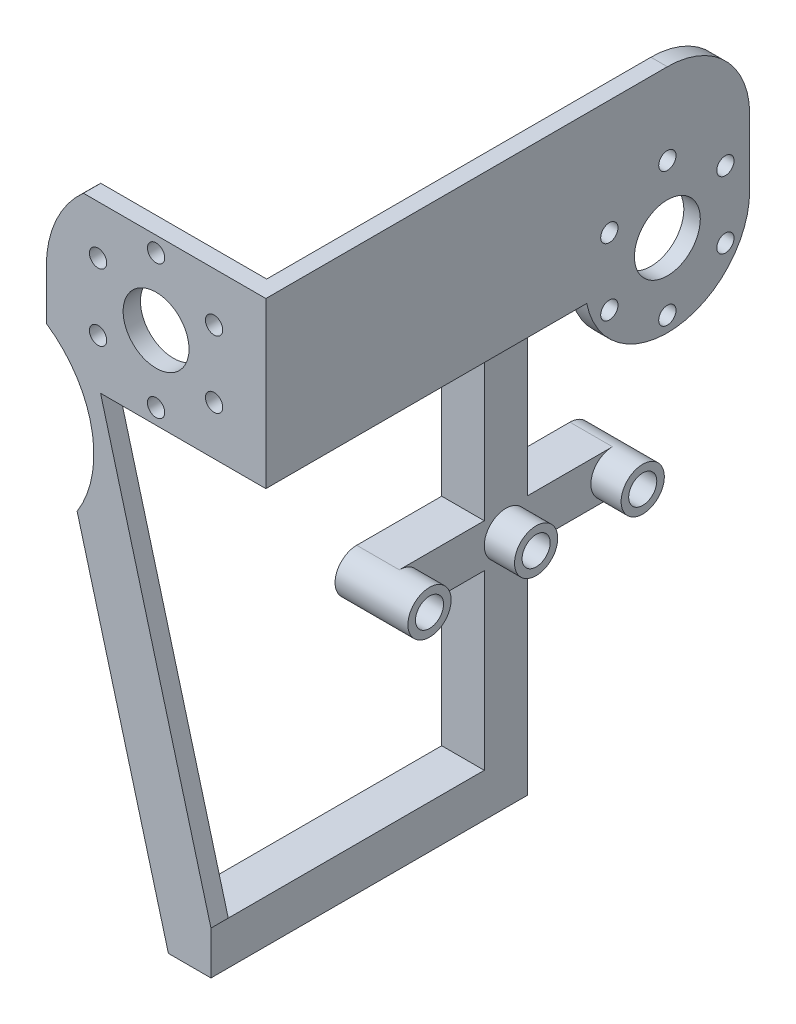
SolidWorks part; units mm, degrees
ref_plane "Front Plane" through (0, 0, 0) normal (0, 0, 1) x (1, 0, 0)
ref_plane "Top Plane" through (0, 0, 0) normal (0, 1, 0) x (1, 0, 0)
ref_plane "Right Plane" through (0, 0, 0) normal (1, 0, 0) x (0, 0, -1)
sketch "Sketch1" plane through (0, 0, 0) normal (0, 0, 1) x (1, 0, 0)
  line L1 (-25.4, -19.05) -> (25.4, -19.05)
  line L2 (-25.4, -19.05) -> (-25.4, 19.05)
  line L3 (-25.4, 19.05) -> (25.4, 19.05)
  line L4 (25.4, -19.05) -> (25.4, 19.05)
  line L5 (-25.4, -19.05) -> (25.4, 19.05) construction
  line L6 (-25.4, 19.05) -> (25.4, -19.05) construction
  circle A0 centre (0, 0) radius 15.5 construction
  circle A1 centre (0, 15.5) radius 2
  circle A2 centre (13.4234, 7.75) radius 2
  circle A3 centre (13.4234, -7.75) radius 2
  circle A4 centre (0, -15.5) radius 2
  circle A5 centre (-13.4234, -7.75) radius 2
  circle A6 centre (-13.4234, 7.75) radius 2
  circle A7 centre (0, 0) radius 7.62
  point P0 (0, 0)
  point P22 (0, 0)
  dimension "D2" = 31
  dimension "D3" = 4
  dimension "D5" = 15.24
  dimension "D1" = 38.1
  dimension "D6" = 50.8
  dimension "D4" = 6
extrude "Boss-Extrude1" add sketch "Sketch1" along normal blind 4
sketch "Sketch2" plane through (0, 0, 4) normal (0, 0, 1) x (1, 0, 0)
  line L2 (-16.8005, 19.05) -> (-25.4, 19.05)
  line L3 (-25.4, 19.05) -> (-25.4, 0)
  line L7 (25.4, 19.05) -> (-25.4, 19.05) construction
  arc A0 (-16.8005, 19.05) -> (-25.4, 0) centre (0, 0) ccw
  point P2 (-19.05, 0)
  point P3 (0, 19.05)
  point P4 (-4.1205, 19.05)
  point P5 (0, 0)
  point P6 (-16.8005, 19.05)
extrude "Cut-Extrude1" cut sketch "Sketch2" against normal up to next
sketch "Sketch4" plane through (25.4, 0, 0) normal (1, 0, 0) x (0, 0, -1)
  line L0 (-4, -19.05) -> (0, -19.05) construction
  line L1 (-4, 19.05) -> (88.9, 19.05)
  line L2 (-4, 19.05) -> (-4, -19.05)
  line L3 (-4, -19.05) -> (88.9, -19.05)
  line L4 (88.9, 19.05) -> (88.9, -19.05)
  line L5 (0, -19.05) -> (0, 19.05) construction
  line L7 (107.95, 0) -> (69.85, 0)
  line L8 (107.95, 0) -> (107.95, -15.24)
  line L9 (107.95, -15.24) -> (69.85, -15.24)
  line L10 (69.85, 0) -> (69.85, -15.24)
  circle A0 centre (88.9, 0) radius 19.05
  circle A1 centre (88.9, -15.24) radius 19.05
  dimension "D1" = 88.9
  dimension "D2" = 15.24
extrude "Boss-Extrude2" add sketch "Sketch4" against normal blind 3.81 contours L2 L1 L4 L3 | A0 | L8 L7 L10 L9 | A1
sketch "Sketch5" plane through (25.4, 0, 0) normal (1, 0, 0) x (0, 0, -1)
  circle A0 centre (88.9, -15.24) radius 7.62
  circle A2 centre (88.9, -15.24) radius 15.5 construction
  circle A3 centre (88.9, 0.26) radius 2
  circle A4 centre (102.3234, -7.49) radius 2
  circle A5 centre (102.3234, -22.99) radius 2
  circle A6 centre (88.9, -30.74) radius 2
  circle A7 centre (75.4766, -22.99) radius 2
  circle A8 centre (75.4766, -7.49) radius 2
  arc A9 (70.2349, -19.05) -> (107.95, -15.24) centre (88.9, -15.24) ccw construction
  dimension "D1" = 15.24
  dimension "D2" = 31
  dimension "D3" = 4
  dimension "D4" = 6
extrude "Cut-Extrude2" cut sketch "Sketch5" against normal up to next
sketch "Sketch6" plane through (0, -19.05, 0) normal (0, -1, 0) x (1, 0, 0)
  line L0 (25.4, 4) -> (25.4, -70.2349) construction
  line L1 (25.4, -59.2349) -> (6.35, -59.2349)
  line L2 (25.4, -59.2349) -> (25.4, -69.2349)
  line L3 (25.4, -69.2349) -> (6.35, -69.2349)
  line L4 (6.35, -59.2349) -> (6.35, -69.2349)
  line L5 (25.4, -70.2349) -> (21.59, -70.2349) construction
  dimension "D1" = 10
  dimension "D2" = 19.05
  dimension "D3" = 1
extrude "Boss-Extrude3" add sketch "Sketch6" against normal blind 10
sketch "Sketch9" plane through (6.35, 0, 0) normal (-1, 0, 0) x (0, 0, 1)
  line L0 (-59.2349, -9.05) -> (-59.2349, -19.05) construction
  line L1 (-69.2349, -9.05) -> (-59.2349, -9.05)
  line L2 (-69.2349, -9.05) -> (-69.2349, -63.45)
  line L3 (-88.9, -73.45) -> (-39.5698, -73.45)
  line L4 (-59.2349, -9.05) -> (-59.2349, -63.45)
  line L5 (-64.2349, -9.05) -> (-64.2349, -73.45) construction
  line L6 (-88.9, -7.62) -> (-88.9, -22.86) construction
  line L7 (-59.2349, -63.45) -> (-39.5698, -63.45)
  line L8 (-64.2349, -63.45) -> (-64.2349, -73.45)
  line L9 (-64.2349, -73.45) -> (-39.5698, -73.45)
  line L11 (-69.2349, -63.45) -> (-88.9, -63.45)
  line L12 (-64.2349, -63.45) -> (-64.2349, -73.45)
  line L13 (-64.2349, -73.45) -> (-88.9, -73.45)
  circle A0 centre (-88.9, -15.24) radius 7.62 construction
  circle A1 centre (-64.2349, -68.45) radius 5 construction
  circle A2 centre (-64.2349, -68.45) radius 3.25
  arc A3 (-88.9, -63.45) -> (-88.9, -73.45) centre (-88.9, -68.45) ccw
  circle A4 centre (-88.9, -68.45) radius 3.25
  circle A5 centre (-39.5698, -68.45) radius 3.25
  arc A6 (-39.5698, -63.45) -> (-39.5698, -73.45) centre (-39.5698, -68.45) cw
  point P2 (-39.3806, -73.45)
  line M5 (-69.2349, -19.05) -> (-59.2349, -19.05)
  dimension "D2" = 10
  dimension "D3" = 6.5
  dimension "D1" = 58.21
extrude "Boss-Extrude6" add sketch "Sketch9" against normal blind 6.35 and the other way blind 3.5 contours A6 L7 L4 L2 L11 A3 L3 A2 A4 A5 M5 region at (6.35, -55.2699, -64.2349)
sketch "Sketch10" plane through (12.7, 0, 0) normal (1, 0, 0) x (0, 0, -1)
  line L1 (64.2349, -19.05) -> (64.2349, -73.45) construction
  line L3 (69.2349, -63.45) -> (88.9, -63.45) construction
  line L4 (69.2349, -19.05) -> (59.2349, -19.05) construction
  circle A0 centre (64.2349, -68.45) radius 5
  circle A2 centre (64.2349, -68.45) radius 5 construction
  circle A4 centre (64.2349, -68.45) radius 3.25
  circle A5 centre (64.2349, -68.45) radius 3.25 construction
  circle A6 centre (39.5698, -68.45) radius 5
  circle A7 centre (88.9, -68.45) radius 5
  circle A8 centre (88.9, -68.45) radius 3.25 construction
  circle A9 centre (39.5698, -68.45) radius 3.25 construction
  circle A10 centre (88.9, -68.45) radius 3.25
  circle A11 centre (39.5698, -68.45) radius 3.25
  arc A12 (39.5698, -63.45) -> (39.5698, -73.45) centre (39.5698, -68.45) ccw construction
  arc A13 (88.9, -73.45) -> (88.9, -63.45) centre (88.9, -68.45) ccw construction
extrude "Boss-Extrude7" add sketch "Sketch10" along normal blind 7 contours A6 | A11 | A4 | A0 | A10 | A7
sketch "Sketch11" plane through (6.35, 0, 0) normal (-1, 0, 0) x (0, 0, 1)
  line L1 (-69.2349, -9.05) -> (-59.2349, -9.05)
  line L2 (-69.2349, -9.05) -> (-69.2349, -19.05)
  line L3 (-69.2349, -19.05) -> (-59.2349, -19.05)
  line L4 (-59.2349, -9.05) -> (-59.2349, -19.05)
extrude "Boss-Extrude8" add sketch "Sketch11" along normal up to surface (3.5 mm away) up to face at (2.85, -54.85, -64.2349)
sketch "Sketch12" plane through (2.85, 0, 0) normal (-1, 0, 0) x (0, 0, 1)
  line L0 (-88.9, -73.45) -> (-39.5698, -73.45) construction
  line L1 (-69.2349, -73.45) -> (-59.2349, -73.45)
  line L2 (-69.2349, -73.45) -> (-69.2349, -123.45)
  line L3 (-69.2349, -123.45) -> (-59.2349, -123.45)
  line L4 (-59.2349, -73.45) -> (-59.2349, -123.45)
  line L5 (-59.2349, -9.05) -> (-59.2349, -63.45) construction
  line L6 (-69.2349, -9.05) -> (-69.2349, -63.45) construction
  line L7 (4, 0) -> (4, 19.05) construction
  line L8 (-59.2349, -123.45) -> (4, -123.45)
  line L9 (-59.2349, -123.45) -> (-59.2349, -113.45)
  line L10 (-59.2349, -113.45) -> (4, -113.45)
  line L11 (4, -123.45) -> (4, -113.45)
  dimension "D1" = 50
extrude "Boss-Extrude9" add sketch "Sketch12" against normal up to surface (9.85 mm away) contours L9 L8 L11 L10 | L2 L1 L4 L3 up to face at (12.7, -58.07, -64.7349)
sketch "Sketch14" plane through (0, 0, 4) normal (0, 0, 1) x (1, 0, 0)
  line L0 (-25.4, -19.05) -> (2.85, -123.45)
  line L1 (2.85, -123.45) -> (12.7, -113.45)
  line L2 (12.7, -113.45) -> (-12.8441, -19.05)
  line L3 (-12.8441, -19.05) -> (-25.4, -19.05)
  point P4 (-25.4, -19.05)
extrude "Boss-Extrude11" add sketch "Sketch14" against normal up to surface (4 mm away) up to face at (-5.2942, 0.1851, 0)
sketch "Sketch15" plane through (0, 0, 4) normal (0, 0, 1) x (1, 0, 0)
  line L0 (-25.4, 0) -> (-25.4, -19.05) construction
  line L1 (-12.8441, -19.05) -> (25.4, -19.05) construction
  circle A0 centre (-39.4, -32.05) radius 25
  point P3 (-35.7916, -39.7548)
  point P6 (-35.4, -32.2614)
  dimension "D2" = 50
  dimension "D1" = 14
  dimension "D3" = 13
extrude "Cut-Extrude3" cut sketch "Sketch15" against normal up to surface (4 mm away) up to face at (-2.3239, -40.9416, 0)
equation "\"mounting distance\"= 24mm"
equation "\"ded\"= 2mm"
equation "\"rack base distance\"= 3mm"
equation "\"slot depth\"= 1.15in"
equation "\"stand height\"= \"mounting distance\" + \"ded\" + \"rack base distance\" + \"slot depth\""
equation "\"D1@Sketch9\"=\"stand height\""
